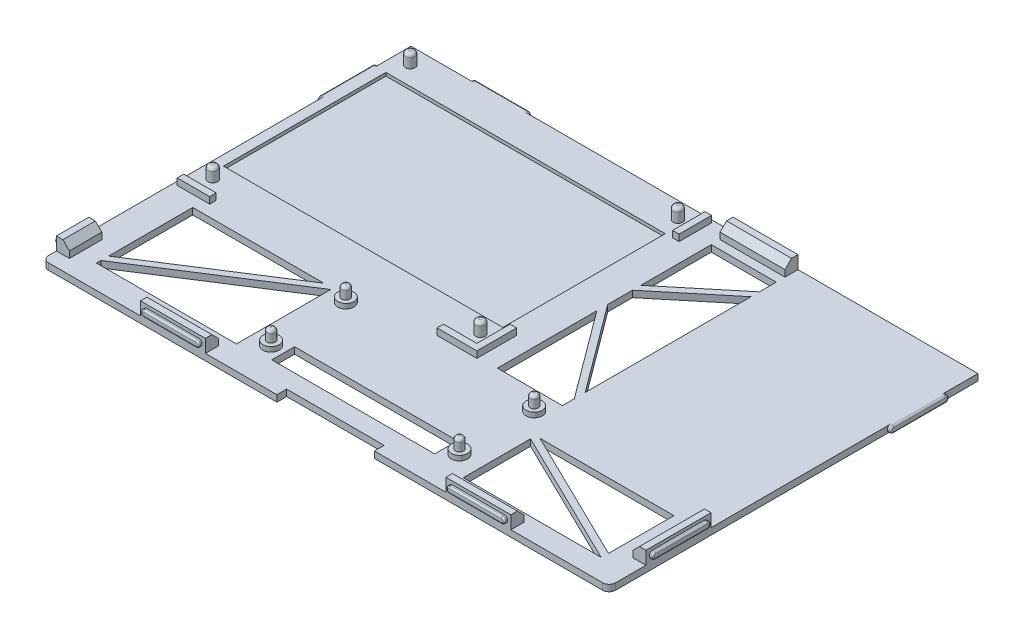
SolidWorks part; units mm, degrees
ref_plane "前基準面" through (0, 0, 0) normal (0, 0, 1) x (1, 0, 0)
ref_plane "上基準面" through (0, 0, 0) normal (0, 1, 0) x (1, 0, 0)
ref_plane "右基準面" through (0, 0, 0) normal (1, 0, 0) x (0, 0, -1)
sketch "草圖1" plane through (0, 0, 0) normal (0, 1, 0) x (1, 0, 0)
  line L0 (0, 56.775) -> (0, -56.775) construction
  line L1 (-87.275, 56.775) -> (87.275, 56.775)
  line L2 (-87.275, 56.775) -> (-87.275, -56.775)
  line L3 (-87.275, -56.775) -> (87.275, -56.775)
  line L4 (87.275, 56.775) -> (87.275, -56.775)
  line L5 (-87.275, 56.775) -> (87.275, -56.775) construction
  line L6 (-87.275, -56.775) -> (87.275, 56.775) construction
  line L7 (-87.275, 0) -> (87.275, 0) construction
  point P0 (0, 0)
  dimension "D1" = 174.55
  dimension "D2" = 113.55
extrude "填料-伸長1" add sketch "草圖1" along normal blind 2
sketch "草圖2" plane through (0, 2, 0) normal (0, 1, 0) x (1, 0, 0)
  line L1 (-86.16, 55.93) -> (3.84, 55.93)
  line L2 (-86.16, 55.93) -> (-86.16, -14.07)
  line L3 (-86.16, -14.07) -> (3.84, -14.07)
  line L4 (3.84, 55.93) -> (3.84, -14.07)
  line L5 (-86.16, 55.93) -> (3.84, -14.07) construction
  line L6 (-86.16, -14.07) -> (3.84, 55.93) construction
  line L8 (-41.16, 55.93) -> (-41.16, -14.07) construction
  line L9 (-86.16, 20.93) -> (3.84, 20.93) construction
  line L10 (0, 56.775) -> (0, -56.775) construction
  line L11 (-87.275, 0) -> (87.275, 0) construction
  point P0 (-41.16, 20.93)
  point P13 (0, 0)
  dimension "D1" = 90
  dimension "D2" = 70
  dimension "D3" = 41.16
  dimension "D4" = 20.93
sketch "草圖3" plane through (0, 2, 0) normal (0, 1, 0) x (1, 0, 0)
  line L0 (3.84, 55.93) -> (3.84, -14.07) construction
  line L1 (4.09, 55.93) -> (6.09, 55.93)
  line L2 (4.09, 55.93) -> (4.09, 45.93)
  line L3 (4.09, 45.93) -> (6.09, 45.93)
  line L4 (6.09, 55.93) -> (6.09, 45.93)
  line L5 (-86.16, -14.07) -> (3.84, -14.07) construction
  line L7 (4.09, -14.07) -> (4.09, -4.07)
  line L8 (4.09, -4.07) -> (6.09, -4.07)
  line L9 (6.09, -14.07) -> (6.09, -4.07)
  line L10 (6.09, -16.32) -> (-6.16, -16.32)
  line L11 (6.09, -16.32) -> (6.09, -15.07)
  line L12 (4.09, -14.32) -> (-6.16, -14.32)
  line L13 (-6.16, -16.32) -> (-6.16, -14.32)
  line L14 (3.84, -14.32) -> (3.84, -16.32) construction
  line L15 (4.09, -14.07) -> (4.09, -14.32)
  line L16 (6.09, -14.07) -> (6.09, -15.07)
  line L18 (-86.16, -16.32) -> (-76.16, -16.32)
  line L19 (-86.16, -16.32) -> (-86.16, -14.32)
  line L20 (-86.16, -14.32) -> (-76.16, -14.32)
  line L21 (-76.16, -16.32) -> (-76.16, -14.32)
  dimension "D1" = 2
  dimension "D2" = 10
  dimension "D3" = 0.25
  dimension "D4" = 2
  dimension "D5" = 2
  dimension "D6" = 2
  dimension "D8" = 0.25
  dimension "D9" = 10
  dimension "D11" = 10
extrude "填料-伸長2" add sketch "草圖3" along normal blind 2
sketch "草圖4" plane through (0, 2, 0) normal (0, 1, 0) x (1, 0, 0)
  line L1 (-86.16, 55.93) -> (3.84, 55.93) construction
  line L2 (3.84, 55.93) -> (3.84, -14.07) construction
  line L3 (-86.16, -14.07) -> (3.84, -14.07) construction
  line L4 (-41.16, 55.93) -> (-41.16, -14.07) construction
  circle A0 centre (0.04, 51.63) radius 1.45
  circle A1 centre (0.04, -9.17) radius 1.45
  circle A2 centre (-82.36, -9.17) radius 1.45
  circle A3 centre (-82.36, 51.63) radius 1.45
  dimension "D1" = 2.9
  dimension "D2" = 3.8
  dimension "D3" = 4.3
  dimension "D4" = 4.9
extrude "填料-伸長3" add sketch "草圖4" along normal blind 4
fillet "圓角2" radius 1 4 edges at (-82.36, 6, -53.08) (-82.36, 6, 7.72) (0.04, 6, 10.62) (0.04, 6, -50.18)
sketch "草圖6" plane through (0, 2, 0) normal (0, 1, 0) x (1, 0, 0)
  line L1 (35.1797, 56.0179) -> (85.1797, 56.0179)
  line L2 (35.1797, 56.0179) -> (35.1797, -24.9821)
  line L3 (35.1797, -24.9821) -> (85.1797, -24.9821)
  line L4 (85.1797, 56.0179) -> (85.1797, -24.9821)
  line L5 (35.1797, 56.0179) -> (85.1797, -24.9821) construction
  line L6 (35.1797, -24.9821) -> (85.1797, 56.0179) construction
  point P0 (60.1797, 15.5179)
  dimension "D1" = 81
  dimension "D2" = 50
sketch "草圖5" plane through (0, 2, 0) normal (0, 1, 0) x (1, 0, 0)
  line L0 (-86.16, 55.93) -> (3.84, -14.07) construction
  line L1 (-84.16, 45.93) -> (1.84, 45.93)
  line L2 (-84.16, 45.93) -> (-84.16, -4.07)
  line L3 (-84.16, -4.07) -> (1.84, -4.07)
  line L4 (1.84, 45.93) -> (1.84, -4.07)
  line L5 (-84.16, 45.93) -> (1.84, -4.07) construction
  line L6 (-84.16, -4.07) -> (1.84, 45.93) construction
  line L7 (-86.16, 55.93) -> (3.84, 55.93) construction
  line L8 (-86.16, 55.93) -> (-86.16, -14.07) construction
  point P0 (-41.16, 20.93)
  dimension "D1" = 10
  dimension "D2" = 2
extrude "除料-伸長1" cut sketch "草圖5" against normal blind 1
sketch "草圖7" plane through (0, 2, 0) normal (0, 1, 0) x (1, 0, 0)
  line L0 (0, 56.775) -> (0, -56.775) construction
  line L1 (-32.5, -18.075) -> (32.5, -18.075)
  line L2 (-32.5, -18.075) -> (-32.5, -48.275)
  line L3 (-32.5, -48.275) -> (32.5, -48.275)
  line L4 (32.5, -18.075) -> (32.5, -48.275)
  line L5 (-32.5, -18.075) -> (32.5, -48.275) construction
  line L6 (-32.5, -48.275) -> (32.5, -18.075) construction
  line L7 (-87.275, -56.775) -> (87.275, -56.775) construction
  point P0 (0, -33.175)
  point P5 (32.5, -33.175)
  dimension "D1" = 65
  dimension "D2" = 30.2
  dimension "D3" = 8.5
sketch "草圖8" plane through (0, 2, 0) normal (0, 1, 0) x (1, 0, 0)
  line L0 (-32.5, -18.075) -> (32.5, -18.075) construction
  line L1 (32.5, -18.075) -> (32.5, -48.275) construction
  line L2 (-32.5, -48.275) -> (32.5, -48.275) construction
  line L3 (0, -18.075) -> (0, -48.275) construction
  circle A0 centre (29, -21.575) radius 2.5
  circle A1 centre (29, -21.575) radius 1.25
  circle A2 centre (29, -44.575) radius 2.5
  circle A3 centre (29, -44.575) radius 1.25
  circle A4 centre (-29, -44.575) radius 1.25
  circle A5 centre (-29, -44.575) radius 2.5
  circle A6 centre (-29, -21.575) radius 1.25
  circle A7 centre (-29, -21.575) radius 2.5
  dimension "D1" = 5
  dimension "D4" = 2.5
  dimension "D2" = 3.5
  dimension "D3" = 3.5
  dimension "D5" = 3.7
extrude "填料-伸長4" add sketch "草圖8" along normal blind 1.5 contours A6 | A7 A6 | A5 A4 | A4 | A0 A1 | A1 | A2 A3 | A3 region at (26.5707, 2, 21.575) region at (29, 2, 21.575) region at (26.5707, 2, 44.575) region at (29, 2, 44.575) region at (-29, 2, 44.575) region at (-31.4293, 2, 44.575) region at (-29, 2, 21.575) region at (-31.4293, 2, 21.575)
extrude "填料-伸長5" add sketch "草圖8<3>" along normal blind 5 contours A6 | A4 | A3 | A1 region at (29, 2, 21.575) region at (29, 2, 44.575) region at (-29, 2, 44.575) region at (-29, 2, 21.575)
sketch "草圖8<3>" plane through (0, 2, 0) normal (0, 1, 0) x (1, 0, 0) same geometry as "草圖8"
fillet "圓角3" radius 1 4 edges at (-29, 7, 45.825) (29, 7, 45.825) (29, 7, 22.825) (-29, 7, 22.825)
sketch "草圖9" plane through (0, 2, 0) normal (0, 1, 0) x (1, 0, 0)
  line L0 (0, 56.775) -> (0, -56.775) construction
  line L1 (-25.0798, -41.275) -> (25.0798, -41.275)
  line L2 (-25.0798, -41.275) -> (-25.0798, -48.275)
  line L3 (-25.0798, -48.275) -> (25.0798, -48.275)
  line L4 (25.0798, -41.275) -> (25.0798, -48.275)
  line L5 (-25.0798, -41.275) -> (25.0798, -48.275) construction
  line L6 (-25.0798, -48.275) -> (25.0798, -41.275) construction
  line L7 (-32.5, -48.275) -> (32.5, -48.275) construction
  line L8 (-87.275, -56.775) -> (87.275, -56.775) construction
  line L9 (-15, -53.775) -> (15, -53.775)
  line L10 (-15, -53.775) -> (-15, -56.775)
  line L11 (-15, -56.775) -> (15, -56.775)
  line L12 (15, -53.775) -> (15, -56.775)
  line L13 (-15, -53.775) -> (15, -56.775) construction
  line L14 (-15, -56.775) -> (15, -53.775) construction
  point P0 (0, -44.775)
  point P9 (0, -55.275)
  dimension "D1" = 7
  dimension "D2" = 3
  dimension "D3" = 30
extrude "除料-伸長2" cut sketch "草圖9" against normal blind 2
sketch "草圖10" plane through (0, 2, 0) normal (0, 1, 0) x (1, 0, 0)
  line L0 (-87.275, 56.775) -> (87.275, 56.775) construction
  line L1 (11.8547, 56.775) -> (31.8547, 56.775)
  line L2 (11.8547, 56.775) -> (11.8547, 52.775)
  line L3 (11.8547, 52.775) -> (31.8547, 52.775)
  line L4 (31.8547, 56.775) -> (31.8547, 52.775)
  line L5 (0, 56.775) -> (0, -56.775) construction
  line L10 (87.275, 56.775) -> (87.275, -56.775) construction
  line L11 (87.275, -25.438) -> (83.275, -25.438)
  line L12 (87.275, -25.438) -> (87.275, -45.438)
  line L13 (87.275, -45.438) -> (83.275, -45.438)
  line L14 (83.275, -25.438) -> (83.275, -45.438)
  line L15 (-87.275, -56.775) -> (87.275, -56.775) construction
  line L16 (37.0319, -56.775) -> (57.0319, -56.775)
  line L17 (37.0319, -56.775) -> (37.0319, -52.775)
  line L18 (37.0319, -52.775) -> (57.0319, -52.775)
  line L19 (57.0319, -56.775) -> (57.0319, -52.775)
  line L20 (-57.0319, -56.775) -> (-57.0319, -52.775)
  line L21 (-37.0319, -52.775) -> (-57.0319, -52.775)
  line L22 (-37.0319, -56.775) -> (-37.0319, -52.775)
  line L23 (-37.0319, -56.775) -> (-57.0319, -56.775)
  line L24 (-87.275, 56.775) -> (-87.275, -56.775) construction
  line L25 (-87.275, -52.4) -> (-83.275, -52.4)
  line L26 (-87.275, -52.4) -> (-87.275, -42.4)
  line L27 (-87.275, -42.4) -> (-83.275, -42.4)
  line L28 (-83.275, -52.4) -> (-83.275, -42.4)
  dimension "D1" = 4
  dimension "D2" = 20
  dimension "D3" = 4
  dimension "D4" = 10
  dimension "D5" = 20
  dimension "D6" = 4
  dimension "D7" = 20
  dimension "D8" = 4
  dimension "D9" = 99.175
  dimension "D10" = 82.213
extrude "填料-伸長6" add sketch "草圖10" along normal blind 4
sketch "草圖11" plane through (0, 2, 0) normal (0, 1, 0) x (1, 0, 0)
  line L0 (-77.8796, -45.7226) -> (-37.4971, -19.8239)
  line L1 (-77.8796, -49.4672) -> (-34.7645, -49.4672)
  line L2 (-77.8796, -49.4672) -> (-77.8796, -48.0986)
  line L3 (-77.8796, -19.8239) -> (-37.4971, -19.8239)
  line L4 (-34.7645, -49.4672) -> (-34.7645, -20.4474)
  line L5 (-77.8796, -48.0986) -> (-34.7645, -20.4474)
  line L6 (-77.8796, -45.7226) -> (-77.8796, -19.8239)
  line L7 (31.8547, 44.9175) -> (11.8547, 28.4103)
  line L8 (11.8547, 50.0907) -> (31.8547, 50.0907)
  line L9 (11.8547, 50.0907) -> (11.8547, 28.4103)
  line L10 (11.8547, -15.7529) -> (31.8547, -15.7529)
  line L11 (31.8547, 50.0907) -> (31.8547, 44.9175)
  line L13 (11.8547, 25.8171) -> (31.8547, 42.3243)
  line L14 (11.8547, 18.1985) -> (31.8547, -8.7367)
  line L15 (11.8547, 14.8436) -> (31.8547, -12.0916)
  line L16 (31.8547, 42.3243) -> (31.8547, -8.7367)
  line L17 (11.8547, 25.8171) -> (11.8547, 18.1985)
  line L18 (11.8547, 14.8436) -> (11.8547, -15.7529)
  line L19 (31.8547, -12.0916) -> (31.8547, -15.7529)
  line L20 (78.3594, -48.0628) -> (37.1158, -27.9151)
  line L21 (37.1158, -27.9151) -> (78.3594, -27.9151)
  line L22 (35.8042, -29.5002) -> (35.8042, -50.2291)
  line L23 (35.8042, -50.2291) -> (78.2374, -50.2291)
  line L24 (78.3594, -27.9151) -> (78.3594, -48.0628)
  line L25 (35.8042, -29.5002) -> (78.2374, -50.2291)
  dimension "D1" = 2
  dimension "D2" = 2
  dimension "D3" = 2
  dimension "D4" = 2
extrude "除料-伸長3" cut sketch "草圖11" against normal through all
fillet "圓角1" radius 2 2 edges at (-87.275, 1, 56.775) (87.275, 1, 56.775)
chamfer "導角1" distance 2 angle 45 5 edges at (83.275, 6, 35.438) (47.0319, 6, 52.775) (-47.0319, 6, 52.775) (-83.275, 6, 47.4) (21.8547, 6, -52.775)
sketch "草圖13" plane through (87.275, 0, 0) normal (1, 0, 0) x (0, 0, -1)
  line L0 (-43.438, 4) -> (-27.438, 4) construction
  line L1 (-43.438, 5) -> (-27.438, 5)
  line L2 (-43.438, 3) -> (-27.438, 3)
  line L4 (-45.438, 4) -> (-25.438, 4) construction
  line L5 (-45.438, 6) -> (-45.438, 2) construction
  arc A0 (-43.438, 5) -> (-43.438, 3) centre (-43.438, 4) ccw
  arc A1 (-27.438, 3) -> (-27.438, 5) centre (-27.438, 4) ccw
  point P2 (-35.438, 4)
  point P16 (-35.438, 4)
  dimension "D1" = 2
  dimension "D2" = 16
extrude "填料-伸長8" add sketch "草圖13" along normal blind 1
sketch "草圖14" plane through (0, 0, -56.775) normal (0, 0, -1) x (-1, 0, 0)
  line L0 (-31.8547, 4) -> (-11.8547, 4) construction
  line L1 (-31.8547, 6) -> (-31.8547, 2) construction
  line L2 (-29.8547, 4) -> (-13.8547, 4) construction
  line L3 (-29.8547, 5) -> (-13.8547, 5)
  line L4 (-29.8547, 3) -> (-13.8547, 3)
  arc A0 (-29.8547, 5) -> (-29.8547, 3) centre (-29.8547, 4) ccw
  arc A1 (-13.8547, 3) -> (-13.8547, 5) centre (-13.8547, 4) ccw
  point P7 (-21.8547, 4)
  point P13 (-21.8547, 4)
  dimension "D1" = 16
  dimension "D2" = 2
extrude "填料-伸長9" add sketch "草圖14" along normal blind 1
sketch "草圖15" plane through (0, 0, 56.775) normal (0, 0, 1) x (1, 0, 0)
  line L0 (-57.0319, 4) -> (-37.0319, 4) construction
  line L1 (-57.0319, 6) -> (-57.0319, 2) construction
  line L2 (-37.0319, 6) -> (-37.0319, 2) construction
  line L3 (-55.0319, 4) -> (-39.0319, 4) construction
  line L4 (-55.0319, 5) -> (-39.0319, 5)
  line L5 (-55.0319, 3) -> (-39.0319, 3)
  line L6 (0, 2) -> (0, 0) construction
  line L7 (55.0319, 4) -> (39.0319, 4) construction
  line L8 (55.0319, 5) -> (39.0319, 5)
  line L9 (55.0319, 3) -> (39.0319, 3)
  arc A0 (-55.0319, 5) -> (-55.0319, 3) centre (-55.0319, 4) ccw
  arc A1 (-39.0319, 3) -> (-39.0319, 5) centre (-39.0319, 4) ccw
  arc A2 (55.0319, 5) -> (55.0319, 3) centre (55.0319, 4) cw
  arc A3 (39.0319, 3) -> (39.0319, 5) centre (39.0319, 4) cw
  point P8 (-47.0319, 4)
  point P16 (47.0319, 4)
  dimension "D1" = 16
  dimension "D2" = 2
extrude "填料-伸長11" add sketch "草圖15" along normal blind 1
sketch "草圖16" plane through (-87.275, 0, 0) normal (-1, 0, 0) x (0, 0, 1)
  line L0 (42.4, 4) -> (52.4, 4) construction
  line L1 (42.4, 6) -> (42.4, 2) construction
  line L2 (52.4, 6) -> (52.4, 2) construction
  line L3 (43.9, 4) -> (50.9, 4) construction
  line L4 (43.9, 5) -> (50.9, 5)
  line L5 (43.9, 3) -> (50.9, 3)
  arc A0 (43.9, 5) -> (43.9, 3) centre (43.9, 4) ccw
  arc A1 (50.9, 3) -> (50.9, 5) centre (50.9, 4) ccw
  point P8 (47.4, 4)
  dimension "D1" = 7
  dimension "D2" = 2
extrude "填料-伸長12" add sketch "草圖16" along normal blind 1
ref_plane "Plane7" through (0, 0, 0) normal (-1, 0, 0) x (0, 0, 1)
sketch "Sketch1" plane through (0, 0, -56.775) normal (0, 0, -1) x (-1, 0, 0)
  line L0 (68.15, 1) -> (52.15, 1) construction
  line L1 (68.15, 0) -> (52.15, 0)
  line L2 (68.15, 2) -> (52.15, 2)
  line L3 (87.275, 2) -> (87.275, 0) construction
  arc A0 (68.15, 0) -> (68.15, 2) centre (68.15, 1) ccw
  arc A1 (52.15, 2) -> (52.15, 0) centre (52.15, 1) ccw
  point P2 (60.15, 1)
  point P7 (87.275, 1)
  point P8 (0, 0)
  dimension "D1" = 16
  dimension "D2" = 2
  dimension "D3" = 60.15
extrude "Boss-Extrude1" add sketch "Sketch1" along normal blind 1
sketch "Sketch2" plane through (87.275, 0, 0) normal (1, 0, 0) x (0, 0, -1)
  line L0 (29.84, 1) -> (45.84, 1) construction
  line L1 (29.84, 2) -> (45.84, 2)
  line L2 (29.84, 0) -> (45.84, 0)
  line L3 (56.775, 0) -> (56.775, 2) construction
  arc A0 (29.84, 2) -> (29.84, 0) centre (29.84, 1) ccw
  arc A1 (45.84, 0) -> (45.84, 2) centre (45.84, 1) ccw
  point P2 (37.84, 1)
  point P7 (56.775, 1)
  point P8 (0, 0)
  dimension "D1" = 16
  dimension "D2" = 2
  dimension "D3" = 37.84
extrude "Boss-Extrude2" add sketch "Sketch2" along normal blind 1
mirror "Mirror1" about plane through (0, 0, 0) normal (-1, 0, 0) of "Boss-Extrude2"
fillet "圓角4" radius 0.5 32 edges at (12.8547, 4, -57.775) (21.8547, 3, -57.775) (30.8547, 4, -57.775) (88.275, 4, 26.438) (88.275, 3, 35.438) (88.275, 4, 44.438) (56.0319, 4, 57.775) (47.0319, 3, 57.775) (38.0319, 4, 57.775) (-88.275, 4, 51.9) (-88.275, 3, 47.4) (-88.275, 4, 42.9) (-38.0319, 4, 57.775) (-47.0319, 3, 57.775) (-56.0319, 4, 57.775) (21.8547, 5, -57.775) (88.275, 5, 35.438) (47.0319, 5, 57.775) (-88.275, 5, 47.4) (-47.0319, 5, 57.775) (-88.275, 1, -46.84) (-88.275, 0, -37.84) (-88.275, 1, -28.84) (88.275, 1, -46.84) (88.275, 0, -37.84) (88.275, 1, -28.84) (-69.15, 1, -57.775) (-60.15, 0, -57.775) (-51.15, 1, -57.775) (-88.275, 2, -37.84) (88.275, 2, -37.84) (-60.15, 2, -57.775)
